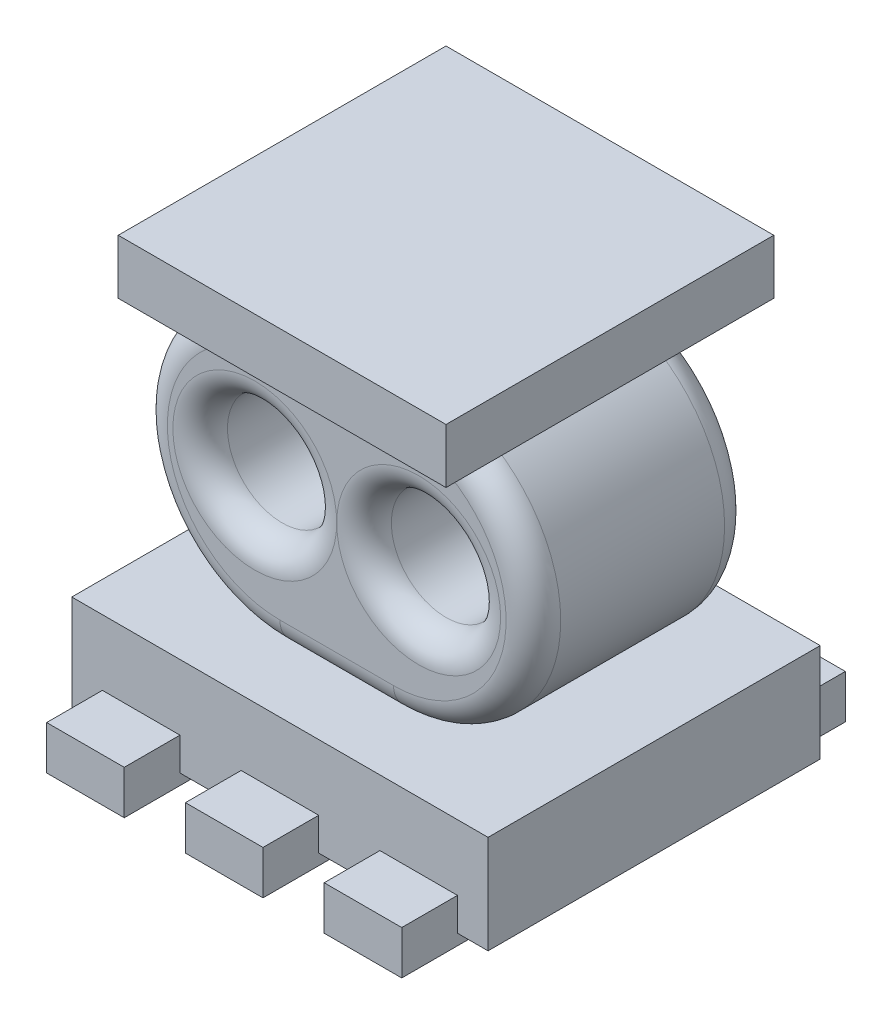
SolidWorks part; units mm, degrees
ref_plane "Спереди" through (0, 0, 0) normal (0, 0, 1) x (1, 0, 0)
ref_plane "Сверху" through (0, 0, 0) normal (0, 1, 0) x (1, 0, 0)
ref_plane "Справа" through (0, 0, 0) normal (1, 0, 0) x (0, 0, -1)
sketch "Эскиз1" plane through (0, 0, 0) normal (0, 1, 0) x (1, 0, 0)
  line L1 (-1.905, 1.52) -> (1.905, 1.52)
  line L2 (-1.905, 1.52) -> (-1.905, -1.52)
  line L3 (-1.905, -1.52) -> (1.905, -1.52)
  line L4 (1.905, 1.52) -> (1.905, -1.52)
  line L5 (-1.905, 1.52) -> (1.905, -1.52) construction
  line L6 (-1.905, -1.52) -> (1.905, 1.52) construction
  point P0 (0, 0)
  dimension "D1" = 3.81
  dimension "D2" = 3.04
extrude "Бобышка-Вытянуть1" add sketch "Эскиз1" along normal blind 0.9
sketch "Эскиз2" plane through (0, 0, 0) normal (0, 1, 0) x (1, 0, 0)
  line L0 (0, 0) -> (0, 50000) construction
  line L1 (0, 0) -> (50000, 0) construction
  line L2 (1.27, -0.8135) -> (1.27, 49999.1865) construction
  line L3 (-1.905, -1.52) -> (1.905, -1.52) construction
  line L4 (0.915, -1.01) -> (1.625, -1.01)
  line L5 (0.915, -1.01) -> (0.915, -2.03)
  line L6 (0.915, -2.03) -> (1.625, -2.03)
  line L7 (1.625, -1.01) -> (1.625, -2.03)
  line L8 (0.915, -1.01) -> (1.625, -2.03) construction
  line L9 (0.915, -2.03) -> (1.625, -1.01) construction
  line L10 (-0.915, -2.03) -> (-1.625, -1.01) construction
  line L11 (-0.355, -1.01) -> (0.355, -1.01)
  line L12 (-0.355, -1.01) -> (-0.355, -2.03)
  line L13 (-0.355, -2.03) -> (0.355, -2.03)
  line L14 (0.355, -1.01) -> (0.355, -2.03)
  line L15 (-0.355, -1.01) -> (0.355, -2.03) construction
  line L16 (-0.355, -2.03) -> (0.355, -1.01) construction
  line L17 (-0.915, -1.01) -> (-1.625, -2.03) construction
  line L18 (-1.625, -1.01) -> (-1.625, -2.03)
  line L19 (-0.915, -2.03) -> (-1.625, -2.03)
  line L20 (-0.915, -1.01) -> (-0.915, -2.03)
  line L21 (-0.915, -1.01) -> (-1.625, -1.01)
  line L22 (-0.915, 1.01) -> (-1.625, 2.03) construction
  line L23 (-0.355, 2.03) -> (0.355, 1.01) construction
  line L24 (-0.355, 1.01) -> (0.355, 2.03) construction
  line L25 (-0.915, 2.03) -> (-1.625, 1.01) construction
  line L26 (0.915, 2.03) -> (1.625, 1.01) construction
  line L27 (0.915, 1.01) -> (1.625, 2.03) construction
  line L28 (-0.915, 1.01) -> (-1.625, 1.01)
  line L29 (-0.915, 1.01) -> (-0.915, 2.03)
  line L30 (-0.915, 2.03) -> (-1.625, 2.03)
  line L31 (-1.625, 1.01) -> (-1.625, 2.03)
  line L32 (0.355, 1.01) -> (0.355, 2.03)
  line L33 (-0.355, 2.03) -> (0.355, 2.03)
  line L34 (-0.355, 1.01) -> (-0.355, 2.03)
  line L35 (-0.355, 1.01) -> (0.355, 1.01)
  line L36 (1.625, 1.01) -> (1.625, 2.03)
  line L37 (0.915, 2.03) -> (1.625, 2.03)
  line L38 (0.915, 1.01) -> (0.915, 2.03)
  line L39 (0.915, 1.01) -> (1.625, 1.01)
  point P7 (1.27, -1.52)
  point P12 (0, -1.52)
  point P19 (0, -1.52)
  point P24 (-1.27, -1.52)
  point P37 (-1.27, 1.52)
  point P38 (0, 1.52)
  point P39 (1.27, 1.52)
  dimension "D1" = 1.27
  dimension "D2" = 1.02
  dimension "D3" = 0.71
  dimension "D4" = 4.06
extrude "Бобышка-Вытянуть2" add sketch "Эскиз2" along normal blind 0.3 and the other way blind 0.1
sketch "Эскиз3" plane through (0, 0, 0) normal (0, 0, 1) x (1, 0, 0)
  line L0 (0, 0) -> (0, -50000) construction
  line L1 (-0.52, 2.18) -> (0.52, 2.18) construction
  line L2 (-0.52, 3.46) -> (0.52, 3.46)
  line L3 (-0.52, 0.9) -> (0.52, 0.9)
  line L4 (-1.905, 0.9) -> (1.905, 0.9) construction
  line L5 (0.915, -0.1) -> (1.625, -0.1) construction
  line L6 (-1.5, 3.96) -> (1.5, 3.96)
  line L7 (-1.5, 3.96) -> (-1.5, 3.46)
  line L8 (-1.5, 3.46) -> (1.5, 3.46)
  line L9 (1.5, 3.96) -> (1.5, 3.46)
  line L10 (-1.5, 3.96) -> (1.5, 3.46) construction
  line L11 (-1.5, 3.46) -> (1.5, 3.96) construction
  arc A0 (-0.52, 3.46) -> (-0.52, 0.9) centre (-0.52, 2.18) ccw
  arc A1 (0.52, 0.9) -> (0.52, 3.46) centre (0.52, 2.18) ccw
  circle A2 centre (0.75, 2.18) radius 0.5
  circle A3 centre (-0.75, 2.18) radius 0.5
  point P5 (0, 2.18)
  point P12 (0, 3.71)
  point P21 (0, 0)
  dimension "D4" = 3.6
  dimension "D5" = 1
  dimension "D6" = 1.5
  dimension "D1" = 3
  dimension "D2" = 0.5
  dimension "D3" = 4.06
extrude "Бобышка-Вытянуть3" add sketch "Эскиз3" against normal mid plane 2 separate body contours L3 A1 L2 A0 region at (0, 2.18, 0)
extrude "Бобышка-Вытянуть4" add sketch "Эскиз3<3>" along normal mid plane 3 separate body contours L9 L6 L7 L8 L2 region at (0, 3.71, 0)
sketch "Эскиз3<3>" plane through (0, 0, 0) normal (0, 0, 1) x (1, 0, 0) same geometry as "Эскиз3"
fillet "Скругление2" radius 0.25 12 edges at (0, 0.9, 1) (-1.8, 2.18, 1) (0, 3.46, 1) (0, 0.9, -1) (-1.8, 2.18, -1) (0, 3.46, -1) (1.25, 2.18, 1) (1.25, 2.18, -1) (-0.25, 2.18, 1) (-0.25, 2.18, -1) (1.8, 2.18, 1) (1.8, 2.18, -1)
combine bodies "Соединить1" operation type add bodies to combine 104 105 106
